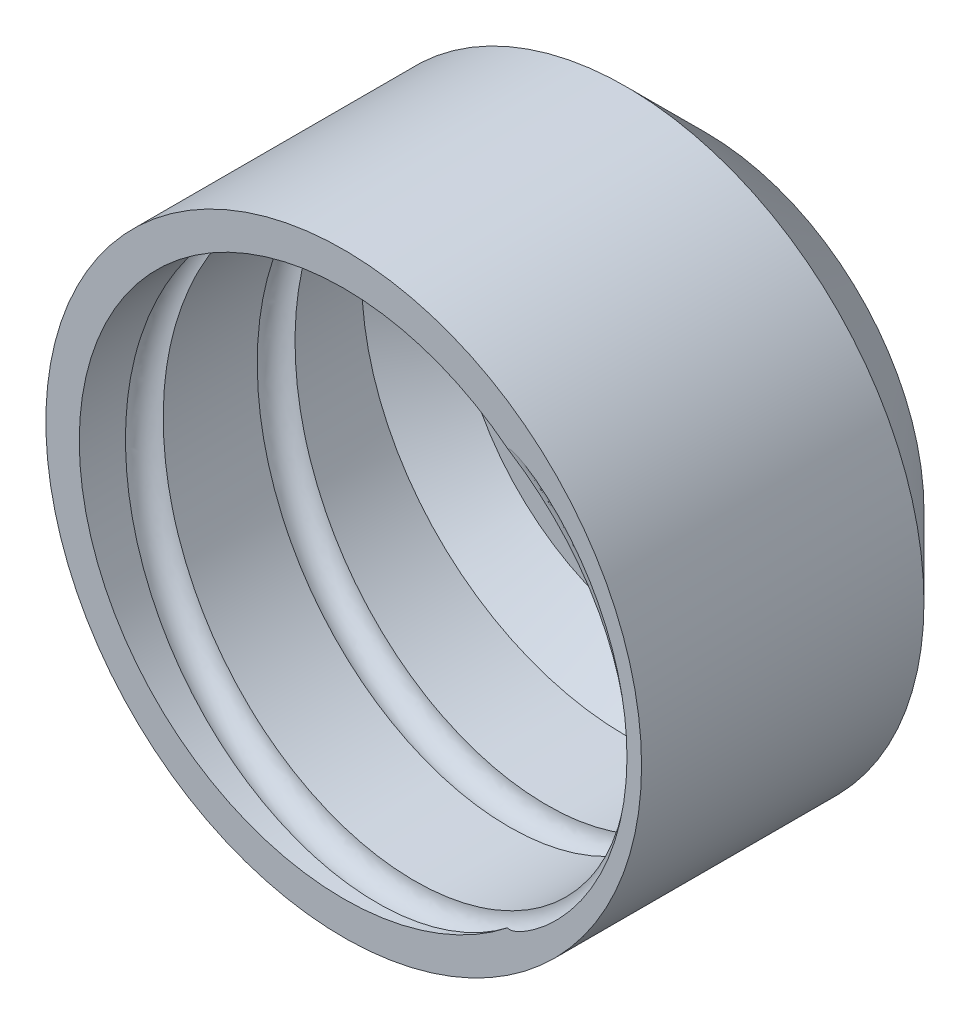
SolidWorks part; units mm, degrees
ref_plane "Front" through (0, 0, 0) normal (0, 0, 1) x (1, 0, 0)
ref_plane "Top" through (0, 0, 0) normal (0, 1, 0) x (1, 0, 0)
ref_plane "Right" through (0, 0, 0) normal (1, 0, 0) x (0, 0, -1)
sketch "Sketch2" plane through (0, 0, 0) normal (1, 0, 0) x (0, 0, -1)
  line L0 (2.2334, 14.7049) -> (-3.1548, 20.093)
  line L1 (0, 0) -> (2.2334, 0)
  line L2 (0, 0) -> (0, 14.6841)
  line L4 (2.2334, 0) -> (2.2334, 14.7049)
  line L5 (0, 14.6841) -> (-3.1548, 17.8389)
  line L7 (-3.1548, 17.8389) -> (-22.2048, 17.8389)
  line L8 (-3.1548, 20.093) -> (-22.2048, 20.093)
  line L9 (-22.2048, 20.093) -> (-22.2048, 17.8389)
  point P8 (0, 0)
  point P11 (-3.1548, 0)
revolve "Revolve1" add sketch "Sketch2" angle 360 about L1
ref_plane "Plane1" through (0, 0, 22.2048) normal (0, 0, 1) x (1, 0, 0)
sketch "Sketch5" plane through (0, 0, 22.2048) normal (0, 0, 1) x (1, 0, 0)
  circle A0 centre (0, 0) radius 17.8389
curve "Helix/Spiral1" pitch 8.89 height 17.78 radius 17.8389 centre (0, 0, 22.2048) axis (0, 0, -1) start towards (1, 0, 0)
sweep "Cut-Sweep7" cut path "Helix/Spiral1" align with end faces yes circular profile diameter 2.54 parameters "D3"=2.54
